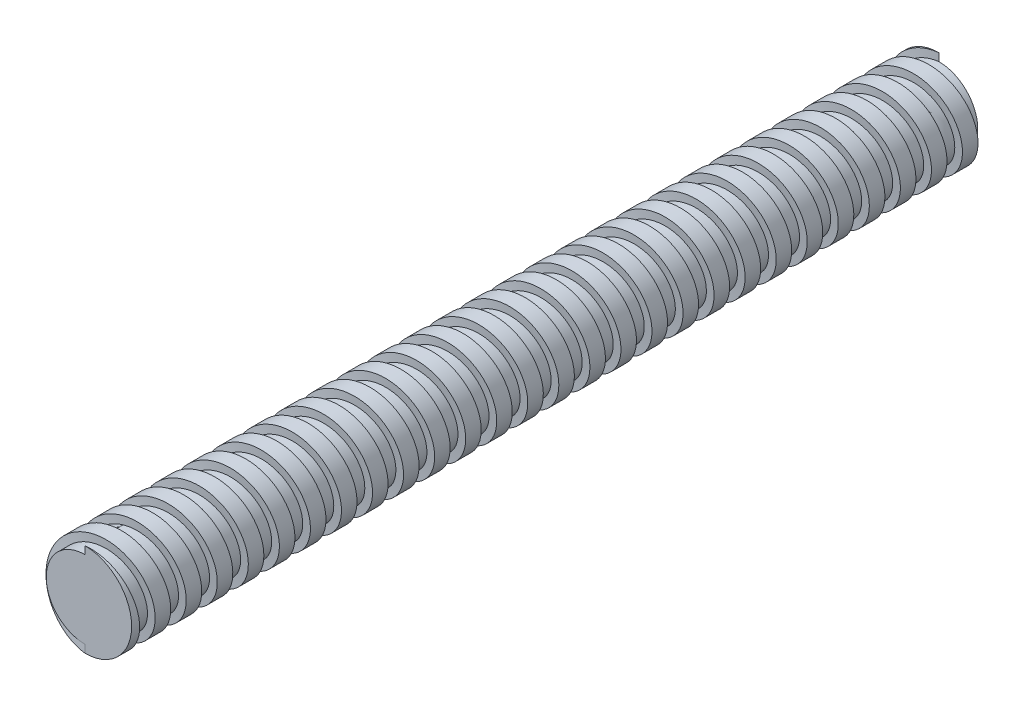
SolidWorks part; units mm, degrees
ref_plane "Front Plane" through (0, 0, 0) normal (0, 0, 1) x (1, 0, 0)
ref_plane "Top Plane" through (0, 0, 0) normal (0, 1, 0) x (1, 0, 0)
ref_plane "Right Plane" through (0, 0, 0) normal (1, 0, 0) x (0, 0, -1)
sketch "Sketch1" plane through (0, 0, 0) normal (0, 0, 1) x (1, 0, 0)
  circle A0 centre (0, 0) radius 3
  dimension "D1" = 6
extrude "Boss-Extrude1" add sketch "Sketch1" along normal blind 55
sketch "Sketch2" plane through (0, 0, 0) normal (1, 0, 0) x (0, 0, -1)
  line L1 (-1, 3) -> (0, 3)
  line L2 (-1, 3) -> (-1, 2.5)
  line L3 (-1, 2.5) -> (0, 2.5)
  line L4 (0, 3) -> (0, 2.5)
  dimension "D1" = 0.5
  dimension "D2" = 1
  dimension "D3" = 3
  dimension "D4" = 0
sketch "Sketch3" plane through (0, 0, 0) normal (0, 0, -1) x (-1, 0, 0)
  circle A0 centre (0, 0) radius 3 construction
  circle A1 centre (0, 0) radius 3
curve "Helix/Spiral1" pitch 2 height 55 turns 27.5
ref_plane "Plane2" through (3, 0, 0) normal (0, 0.9944, 0.1055) x (1, 0, 0)
sweep "Cut-Sweep1" cut profiles "Sketch2" path "Helix/Spiral1" align with end faces yes
sketch "Sketch4" plane through (0, 0, 0) normal (0, 0, -1) x (-1, 0, 0)
  circle A0 centre (0, 0) radius 2.5
  dimension "D1" = 5
